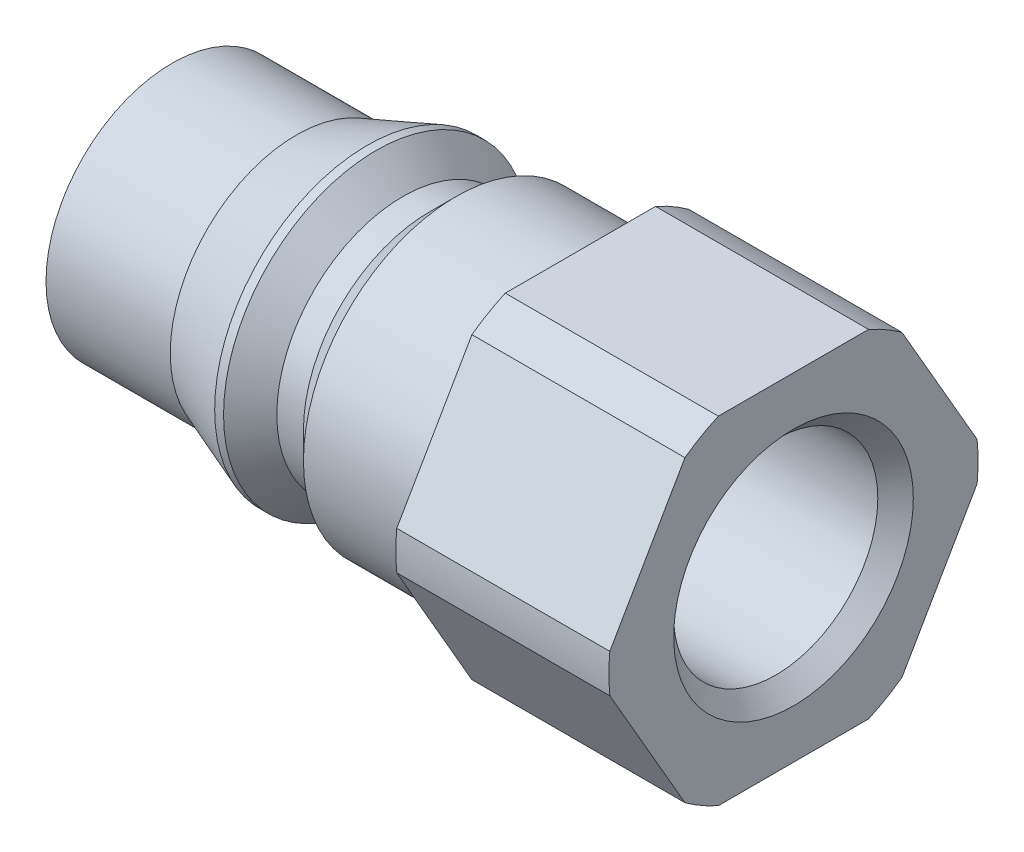
SolidWorks part; units mm, degrees
material "A286, generico"
ref_plane "Front Plane" through (0, 0, 0) normal (0, 0, 1) x (1, 0, 0)
ref_plane "Top Plane" through (0, 0, 0) normal (0, 1, 0) x (1, 0, 0)
ref_plane "Right Plane" through (0, 0, 0) normal (1, 0, 0) x (0, 0, -1)
sketch "Sketch1" plane through (0, 0, 0) normal (0, 0, 1) x (1, 0, 0)
  line L0 (0, -7.1) -> (7, -7.1)
  line L4 (13, -7.1) -> (14.5, -7.1)
  line L5 (14.5, -7.1) -> (16, -8.6)
  line L7 (35, -10.4) -> (35, -3.175)
  line L8 (35, -3.175) -> (0, -3.175)
  line L12 (0, -3.175) -> (0, -7.1)
  line L13 (0, 0) -> (35, 0) construction
  line L14 (7, -7.1) -> (11, -8.6)
  line L15 (11, -8.6) -> (11.5, -8.6)
  line L16 (11.5, -8.6) -> (13, -7.1)
  line L17 (16, -8.6) -> (23, -8.6)
  line L18 (23, -8.6) -> (23, -10.4)
  line L19 (23, -10.4) -> (35, -10.4)
  dimension "D1" = 35
  dimension "D2" = 6.35
  dimension "D3" = 14.2
  dimension "D4" = 20.8
  dimension "D5" = 45
  dimension "D6" = 45
  dimension "D7" = 1.5
  dimension "D8" = 4
  dimension "D9" = 0.5
  dimension "D10" = 1.5
  dimension "D11" = 12
  dimension "D12" = 7
revolve "Revolve1" add sketch "Sketch1" angle 360 about L13
sketch "Sketch2" plane through (35, 0, 0) normal (1, 0, 0) x (0, 0, -1)
  line L1 (-5.4848, 9.5) -> (-10.9697, 0)
  line L2 (-10.9697, 0) -> (-5.4848, -9.5)
  line L3 (-5.4848, -9.5) -> (5.4848, -9.5)
  line L4 (5.4848, -9.5) -> (10.9697, 0)
  line L5 (10.9697, 0) -> (5.4848, 9.5)
  line L6 (5.4848, 9.5) -> (-5.4848, 9.5)
  circle A0 centre (0, 0) radius 9.5 construction
  circle A1 centre (0, 0) radius 10.4 construction
  circle A2 centre (0, 0) radius 10.4
  circle M8 centre (0, 0) radius 10.4
  dimension "D1" = 19
extrude "Cut-Extrude1" cut sketch "Sketch2" against normal through all contours L6 M8 | L1 M8 | L2 M8 | L5 M8 | L4 M8 | L3 M8 region at (35, 4.9307, 8.5402) region at (35, 9.8614, 0) region at (35, -4.9307, 8.5402) region at (35, 4.9307, -8.5402) region at (35, -9.8614, 0) region at (35, -4.9307, -8.5402)
sketch "Schizzo1" plane through (35, 0, 0) normal (1, 0, 0) x (0, 0, -1)
  circle A0 centre (0, 0) radius 5.75
  dimension "D1" = 11.5
extrude "Taglio-Estrusione1" cut sketch "Schizzo1" against normal blind 10
chamfer "Smusso1" distance 1 angle 45 1 edges at (35, 0, -5.75)
